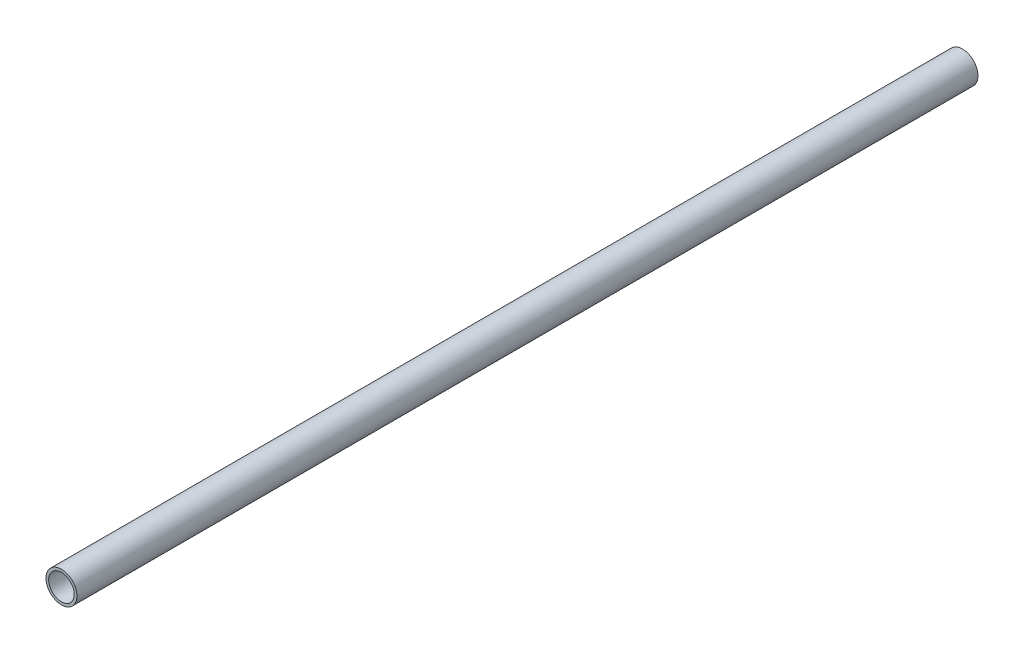
SolidWorks part; units mm, degrees
material "ASTM-A513"
ref_plane "Front Plane" through (0, 0, 0) normal (1, 0, 0) x (0, 1, 0)
ref_plane "Top Plane" through (0, 0, 0) normal (0, 0, 1) x (0, 1, 0)
ref_plane "Right Plane" through (0, 0, 0) normal (0, 1, 0) x (-1, 0, 0)
sketch "Sketch1" plane through (0, 0, 0) normal (0, 0, 1) x (0, 1, 0)
  circle A0 centre (0, 0) radius 17.4625
  circle A1 centre (0, 0) radius 14.4145
  point P3 (0, 0)
  point P4 (0, 0)
  dimension "D1" = 34.925
  dimension "D2" = 3.048
extrude "Boss-Extrude1" add sketch "Sketch1" along normal mid plane 1016
